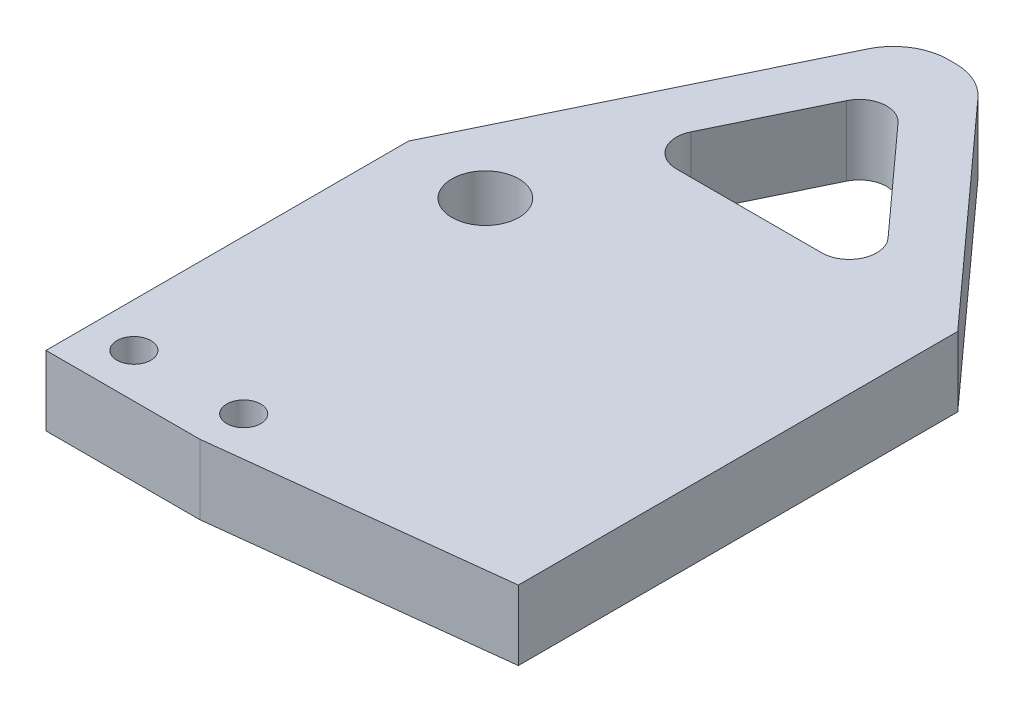
SolidWorks part; units mm, degrees
ref_plane "Front Plane" through (0, 0, 0) normal (0, 0, 1) x (1, 0, 0)
ref_plane "Top Plane" through (0, 0, 0) normal (0, 1, 0) x (1, 0, 0)
ref_plane "Right Plane" through (0, 0, 0) normal (1, 0, 0) x (0, 0, -1)
sketch "Sketch1" plane through (0, 0, 0) normal (0, 1, 0) x (1, 0, 0)
  line L1 (-80, 0) -> (-80, 60)
  line L6 (0, 80) -> (0, 0)
  line L7 (0, 0) -> (-52, -6)
  line L8 (-52, -6) -> (-80, -6)
  line L9 (-80, -6) -> (-80, 0)
  line L10 (-80, 60) -> (-50, 122)
  line L11 (-50, 122) -> (-38, 122)
  line L12 (-38, 122) -> (0, 80)
  circle A0 centre (-64, 58) radius 6.1
  circle A3 centre (-72, 2) radius 3.1
  circle A4 centre (-52, 2) radius 3.1
  dimension "D8" = 12.2
  dimension "D12" = 6.2
  dimension "D16" = 6.2
  dimension "D1" = 80
  dimension "D2" = 80
  dimension "D3" = 60
  dimension "D4" = 62
  dimension "D5" = 30
  dimension "D6" = 12
  dimension "D9" = 16
  dimension "D10" = 6
  dimension "D13" = 8
  dimension "D14" = 8
  dimension "D15" = 20
  dimension "D17" = 58
extrude "Boss-Extrude1" add sketch "Sketch1" along normal blind 12.7
fillet "Fillet1" radius 10 2 edges at (-38, 6.35, -122) (-50, 6.35, -122)
sketch "Sketch3" plane through (0, 12.7, 0) normal (0, 1, 0) x (1, 0, 0)
  line L5 (-13.4855, 80) -> (-43.2795, 112.9302)
  line L6 (-43.2795, 112.9302) -> (-59.2134, 80)
  line L7 (-59.2134, 80) -> (-13.4855, 80)
  line L10 (0, 80) -> (-35.0225, 118.7091) construction
  line L11 (-52.7312, 116.3556) -> (-80, 60) construction
  dimension "D1" = 10
  dimension "D2" = 10
  dimension "D3" = 10
  dimension "D4" = 10
  dimension "D5" = 0
extrude "Cut-Extrude1" cut sketch "Sketch3" against normal through all
fillet "Fillet2" radius 5 3 edges at (-43.2795, 6.35, -112.9302) (-13.4855, 6.35, -80) (-59.2134, 6.35, -80)
